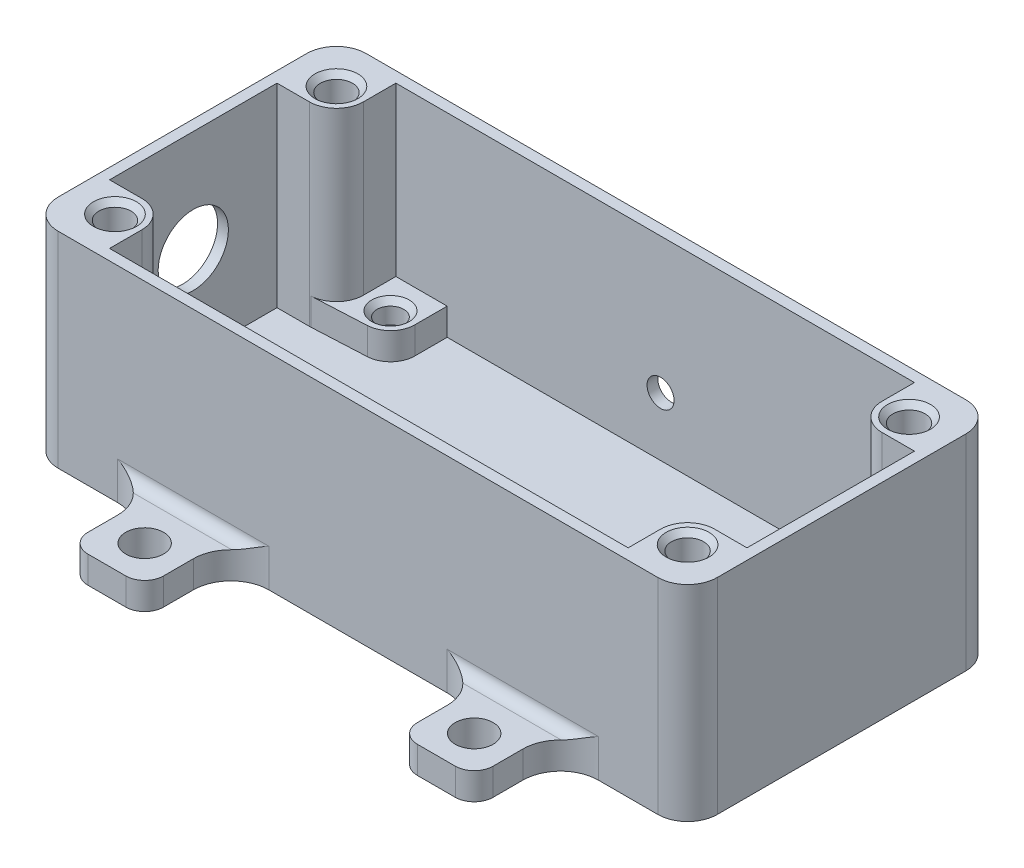
SolidWorks part; units mm, degrees
ref_plane "Front Plane" through (0, 0, 0) normal (0, 0, 1) x (1, 0, 0)
ref_plane "Top Plane" through (0, 0, 0) normal (0, 1, 0) x (1, 0, 0)
ref_plane "Right Plane" through (0, 0, 0) normal (1, 0, 0) x (0, 0, -1)
sketch "Sketch1" plane through (0, 0, 0) normal (0, 1, 0) x (1, 0, 0)
  line L1 (-43, 20.5) -> (43, 20.5) construction
  line L2 (-43, 20.5) -> (-43, -20.5) construction
  line L3 (-43, -20.5) -> (43, -20.5) construction
  line L4 (43, 20.5) -> (43, -20.5) construction
  line L5 (-43, 20.5) -> (43, -20.5) construction
  line L6 (-43, -20.5) -> (43, 20.5) construction
  circle A0 centre (-43, 20.5) radius 4.5
  circle A1 centre (43, 20.5) radius 4.5
  circle A2 centre (43, -20.5) radius 4.5
  circle A3 centre (-43, -20.5) radius 4.5
  point P0 (0, 0)
  dimension "D3" = 9
  dimension "D1" = 41
  dimension "D2" = 86
extrude "Boss-Extrude3" add sketch "Sketch1" along normal blind 7
sketch "Sketch7" plane through (0, 7, 0) normal (0, 1, 0) x (1, 0, 0)
  circle A0 centre (-43, 20.5) radius 2.475
  circle A1 centre (43, 20.5) radius 2.475
  circle A2 centre (43, -20.5) radius 2.475
  circle A3 centre (-43, -20.5) radius 2.475
  dimension "D1" = 4.95
extrude "Cut-Extrude1" cut sketch "Sketch7" against normal blind 4
sketch "Sketch8" plane through (0, 0, 0) normal (0, 1, 0) x (1, 0, 0)
  line L0 (0, 15.6739) -> (0, -18.7807) construction
  line L1 (0, 0) -> (-61.0003, 0) construction
  circle A0 centre (-53, 20.5) radius 5
  circle A1 centre (-53, -20.5) radius 5.5 construction
  circle A2 centre (-53, -20.5) radius 5
  circle A7 centre (-53, 20.5) radius 5.5 construction
  circle A8 centre (-43, 20.5) radius 4.5 construction
  circle A9 centre (53, 20.5) radius 5.5 construction
  circle A10 centre (53, -20.5) radius 5.5 construction
  circle A11 centre (53, -20.5) radius 5
  circle A12 centre (53, 20.5) radius 5
  dimension "D1" = 10
  dimension "D3" = 11
  dimension "D2" = 53
extrude "Boss-Extrude5" add sketch "Sketch8" along normal blind 38
sketch "Sketch9" plane through (0, 38, 0) normal (0, 1, 0) x (1, 0, 0)
  circle A0 centre (-53, 20.5) radius 2.975
  circle A4 centre (-53, -20.5) radius 2.975
  circle A5 centre (53, -20.5) radius 2.975
  circle A6 centre (53, 20.5) radius 2.975
  dimension "D1" = 5.95
extrude "Cut-Extrude2" cut sketch "Sketch9" against normal blind 10 contours A0 | A4 | A6 | A5 region at (-53, 38, -20.5) region at (-53, 38, 20.5) region at (53, 38, 20.5) region at (53, 38, -20.5)
sketch "Sketch10" plane through (0, 0, 0) normal (0, 1, 0) x (1, 0, 0)
  line L5 (-59, 26.5) -> (59, 26.5)
  line L13 (-58, 25.5) -> (58, 25.5) construction
  line L14 (-58, 25.5) -> (-58, -25.5) construction
  line L15 (-58, -25.5) -> (58, -25.5) construction
  line L16 (58, 25.5) -> (58, -25.5) construction
  line L17 (-58, 25.5) -> (58, -25.5) construction
  line L18 (-58, -25.5) -> (58, 25.5) construction
  line L19 (59, 26.5) -> (59, -26.5)
  line L20 (-59, -26.5) -> (59, -26.5)
  line L21 (-59, 26.5) -> (-59, -26.5)
  line L22 (-61, 28.5) -> (61, 28.5)
  line L23 (61, 28.5) -> (61, -28.5)
  line L24 (-61, -28.5) -> (61, -28.5)
  line L25 (-61, 28.5) -> (-61, -28.5)
  circle A2 centre (-53, 20.5) radius 5 construction
  point P0 (0, 0)
  dimension "D1" = 1
  dimension "D2" = 2
extrude "Boss-Extrude12" add sketch "Sketch10" along normal up to surface (38 mm away) separate body up to face at (-53, 38, -17.525)
sketch "Sketch15" plane through (0, 0, 0) normal (0, 1, 0) x (1, 0, 0)
  line L0 (61, -28.5) -> (61, 28.5) construction
  line L1 (-61, -28.5) -> (61, -28.5) construction
  line L2 (-61, 28.5) -> (-61, -28.5) construction
  line L3 (61, 28.5) -> (-61, 28.5) construction
  line L4 (61, -28.5) -> (61, 28.5)
  line L5 (-61, -28.5) -> (61, -28.5)
  line L6 (-61, 28.5) -> (-61, -28.5)
  line L7 (61, 28.5) -> (-61, 28.5)
extrude "Boss-Extrude14" add sketch "Sketch15" along normal blind 2
fillet "Fillet2" radius 5.5 8 edges at (59, 20, 26.5) (61, 19, 28.5) (-61, 19, 28.5) (-59, 20, 26.5) (61, 19, -28.5) (59, 20, -26.5) (-61, 19, -28.5) (-59, 20, -26.5)
sketch "Sketch16" plane through (0, 2, 0) normal (0, 1, 0) x (1, 0, 0)
  line L8 (-59, -21) -> (-59, 21) construction
  line L9 (53.5, 26.5) -> (-53.5, 26.5) construction
  line L10 (-59, 15.5) -> (-59, 21)
  line L11 (-38.5, 26.5) -> (-53.5, 26.5)
  line L12 (-59, 15.5) -> (-53, 15.5)
  line L13 (-52.75, 15.5063) -> (-42.775, 16.0056)
  line L14 (-38.5, 20.5) -> (-38.5, 26.5)
  circle A11 centre (-43, 20.5) radius 2.475 construction
  circle A12 centre (-43, 20.5) radius 4.5 construction
  circle A13 centre (-53, 20.5) radius 2.975 construction
  circle A14 centre (-53, 20.5) radius 5 construction
  arc A15 (-53.5, 26.5) -> (-59, 21) centre (-53.5, 21) ccw construction
  circle A16 centre (-43, 20.5) radius 2.475
  arc A17 (-42.775, 16.0056) -> (-38.5, 20.5) centre (-43, 20.5) ccw
  circle A18 centre (-53, 20.5) radius 2.975
  arc A19 (-53, 15.5) -> (-52.75, 15.5063) centre (-53, 20.5) ccw
  arc A20 (-53.5, 26.5) -> (-59, 21) centre (-53.5, 21) ccw
extrude "Boss-Extrude15" add sketch "Sketch16" along normal up to surface (5 mm away) up to face at (-43, 7, -18.025)
sketch "Sketch17" plane through (0, 7, 0) normal (0, 1, 0) x (1, 0, 0)
  line L0 (-59, 15.5) -> (-53, 15.5)
  line L1 (-59, 21) -> (-59, 15.5) construction
  line L11 (-48, 20.5) -> (-48, 26.5)
  line L12 (-38.5, 26.5) -> (-53.5, 26.5) construction
  line L13 (-48, 26.5) -> (-53.5, 26.5)
  line L14 (-59, 21) -> (-59, 15.5)
  arc A1 (-52.75, 15.5063) -> (-53, 15.5) centre (-53, 20.5) ccw construction
  circle A2 centre (-53, 20.5) radius 2.975 construction
  circle A3 centre (-53, 20.5) radius 2.975
  arc A10 (-53.5, 26.5) -> (-59, 21) centre (-53.5, 21) ccw construction
  arc A11 (-53.5, 26.5) -> (-59, 21) centre (-53.5, 21) ccw
  circle A12 centre (-53, 20.5) radius 5 construction
  arc A13 (-53, 15.5) -> (-48, 20.5) centre (-53, 20.5) ccw
extrude "Boss-Extrude16" add sketch "Sketch17" along normal up to surface (31 mm away) up to face at (-53, 38, -17.525)
mirror "Mirror1" about plane through (0, 0, 0) normal (1, 0, 0) of "Boss-Extrude15", "Boss-Extrude16"
mirror "Mirror2" about plane through (0, 0, 0) normal (0, 0, 1) of "Mirror1"
sketch "Sketch18" plane through (0, 0, -28.5) normal (0, 0, -1) x (-1, 0, 0)
  line L0 (-55.5, 0) -> (55.5, 0) construction
  circle A0 centre (-1, 12.85) radius 2.5
  dimension "D3" = 5
  dimension "D1" = 62
  dimension "D2" = 12.85
extrude "Cut-Extrude3" cut sketch "Sketch18" against normal up to next
sketch "Sketch19" plane through (-61, 0, 0) normal (-1, 0, 0) x (0, 0, 1)
  line L0 (23, 0) -> (23, 38) construction
  circle A0 centre (0, 19) radius 6.5
  point P5 (23, 19)
  dimension "D1" = 13
extrude "Cut-Extrude4" cut sketch "Sketch19" against normal up to next
sketch "Sketch20" plane through (0, 0, 0) normal (0, 1, 0) x (1, 0, 0)
  line L5 (0, 46.5) -> (0, 28.5) construction
  line L6 (55.5, 28.5) -> (-55.5, 28.5) construction
  line L8 (-37.5, 28.5) -> (-23.5, 28.5)
  line L9 (-37.5, 28.5) -> (-37.5, 44.5)
  line L10 (-37.5, 44.5) -> (-23.5, 44.5)
  line L11 (-23.5, 28.5) -> (-23.5, 44.5)
  circle A0 centre (-30.5, 37.5) radius 3.5
  point P9 (-30.5, 44.5)
  point P10 (0, 37.5)
  dimension "D3" = 16
  dimension "D4" = 7
  dimension "D1" = 30.5
  dimension "D2" = 14
  dimension "D6" = 7
extrude "Boss-Extrude17" add sketch "Sketch20" along normal blind 5
mirror "Mirror6" about plane through (0, 0, 0) normal (0, 0, 1) of "Boss-Extrude17"
mirror "Mirror8" about plane through (0, 0, 0) normal (1, 0, 0) of "Mirror6"
fillet "Fillet3" radius 2 4 edges at (-30.5, 5, -28.5) (30.5, 5, -28.5) (30.5, 5, 28.5) (-30.5, 5, 28.5)
fillet "Fillet4" radius 7 8 edges at (-23.5, 3.5, -28.5) (-37.5, 3.5, -28.5) (-37.5, 3.5, 28.5) (-23.5, 3.5, 28.5) (37.5, 3.5, 28.5) (23.5, 3.5, 28.5) (37.5, 3.5, -28.5) (23.5, 3.5, -28.5)
fillet "Fillet5" radius 3.5 8 edges at (-37.5, 2.5, -44.5) (-23.5, 2.5, -44.5) (37.5, 2.5, -44.5) (23.5, 2.5, -44.5) (37.5, 2.5, 44.5) (23.5, 2.5, 44.5) (-23.5, 2.5, 44.5) (-37.5, 2.5, 44.5)
chamfer "Chamfer1" distance 1 angle 45 8 edges at (-43, 7, 22.975) (-43, 7, -18.025) (-53, 38, 23.475) (-53, 38, -17.525) (43, 7, -18.025) (43, 7, 22.975) (53, 38, 23.475) (53, 38, -17.525)
